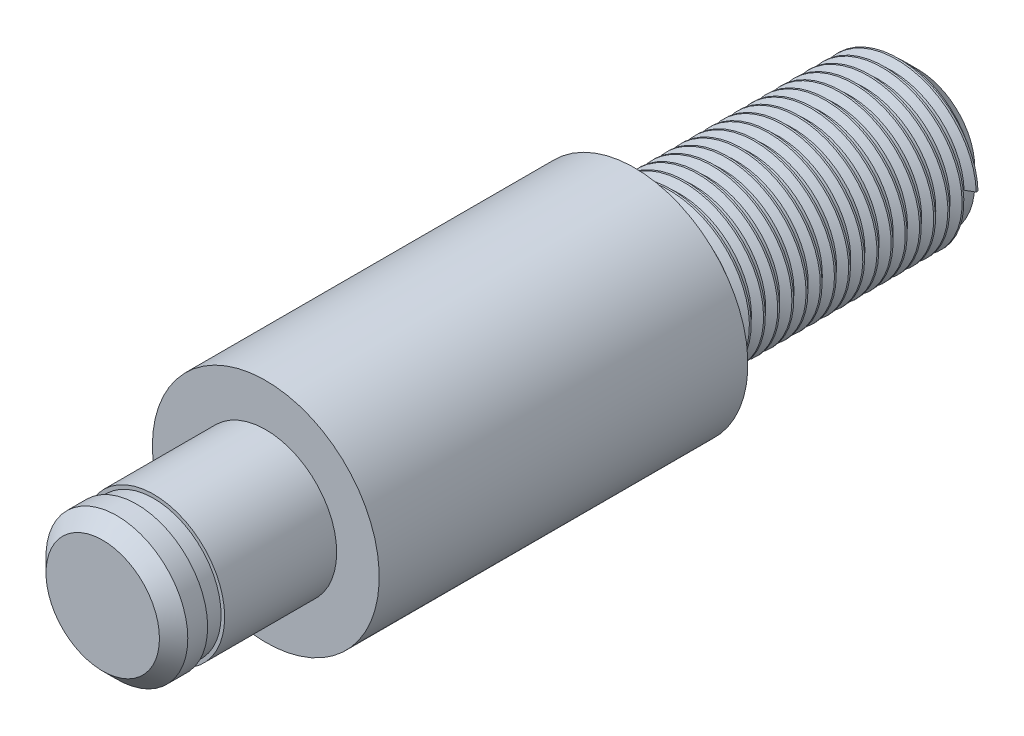
SolidWorks part; units mm, degrees
material "ASTM A36 Steel"
ref_plane "Front Plane" through (0, 0, 0) normal (0, 0, 1) x (1, 0, 0)
ref_plane "Top Plane" through (0, 0, 0) normal (0, 1, 0) x (1, 0, 0)
ref_plane "Right Plane" through (0, 0, 0) normal (1, 0, 0) x (0, 0, -1)
sketch "Sketch1" plane through (0, 0, 0) normal (0, 0, 1) x (1, 0, 0)
  circle A0 centre (0, 0) radius 8
  dimension "D1" = 16
extrude "Boss-Extrude1" add sketch "Sketch1" along normal blind 26
sketch "Sketch2" plane through (0, 0, 26) normal (0, 0, 1) x (1, 0, 0)
  circle A0 centre (0, 0) radius 5
  dimension "D1" = 10
extrude "Boss-Extrude2" add sketch "Sketch2" along normal blind 11.5
sketch "Sketch3" plane through (0, 0, 0) normal (0, 0, -1) x (-1, 0, 0)
  circle A0 centre (0, 0) radius 5
  dimension "D1" = 10
extrude "Boss-Extrude3" add sketch "Sketch3" along normal blind 20
chamfer "Chamfer1" distance 1 angle 45 1 edges at (5, 0, 37.5)
chamfer "Chamfer2" distance 1 angle 45 1 edges at (-5, 0, -20)
thread "Thread1" pitch 1 method extrude profile "Thread Profile1" start angle 0, offset 0, length 18.5, pitch 1, diameter 10
ref_plane "Plane1" through (5, 0, -19) normal (0, -1, 0) x (1, 0, 0)
sketch "Thread Profile1" plane through (5, 0, -19) normal (0, -1, 0) x (1, 0, 0)
  line L0 (0, 0) -> (0, 1) construction
  line L1 (0, 0) -> (0.5413, 0.3125)
  line L2 (0.5413, 0.3125) -> (0.5413, 0.4375)
  line L3 (0.5413, 0.4375) -> (0, 0.75)
  line L4 (0.5413, 0.375) -> (0, 0.375) construction
  line L11 (0, 0) -> (0, 0.75)
  point P2 (0, 0)
  dimension "Pitch" = 1
  dimension "Profile_Angle" = 60
  dimension "Profile_Land" = 0.125
  dimension "Profile_Height" = 0.5413
sketch "Sketch6" plane through (0, 0, 0) normal (0, 1, 0) x (1, 0, 0)
  line L0 (-5, -26) -> (-5, -36.5) construction
  line L1 (-5, -35.1) -> (-4.75, -35.1)
  line L2 (-5, -35.1) -> (-5, -33.9)
  line L3 (-5, -33.9) -> (-4.75, -33.9)
  line L4 (-4.75, -35.1) -> (-4.75, -33.9)
  line L5 (-4, -37.5) -> (4, -37.5) construction
  line L6 (0, -37.5) -> (0, -30.8511)
  dimension "D1" = 2.4
  dimension "D2" = 1.2
  dimension "D3" = 4.75
revolve "Cut-Revolve1" cut sketch "Sketch6" angle 360 about L6 region at (-4.875, 0, 34.5)
